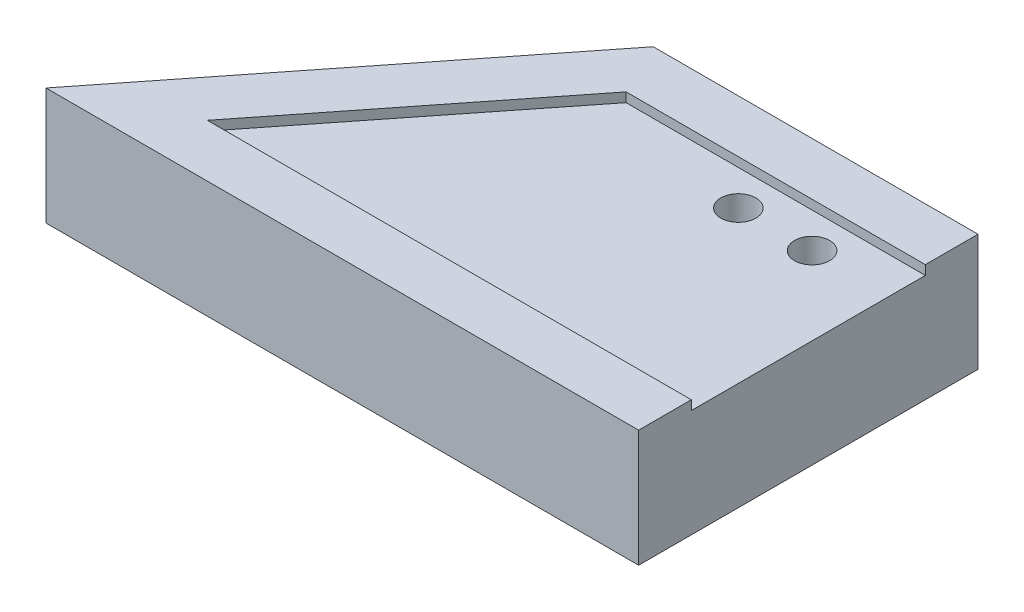
SolidWorks part; units mm, degrees
ref_plane "Front Plane" through (0, 0, 0) normal (0, 0, 1) x (1, 0, 0)
ref_plane "Top Plane" through (0, 0, 0) normal (0, 1, 0) x (1, 0, 0)
ref_plane "Right Plane" through (0, 0, 0) normal (1, 0, 0) x (0, 0, -1)
sketch "Sketch1" plane through (0, 0, 0) normal (0, 1, 0) x (1, 0, 0)
  line L0 (0, 0) -> (61, 0)
  line L1 (61, 0) -> (46, 19)
  line L2 (46, 19) -> (15, 19)
  line L3 (15, 19) -> (0, 0)
  line L4 (12.577, 24) -> (-10.3177, -5)
  line L5 (-10.3177, -5) -> (71.3177, -5)
  line L6 (71.3177, -5) -> (48.423, 24)
  line L7 (48.423, 24) -> (12.577, 24)
  point P3 (30.5, 19)
  point P7 (30.5, 0)
  dimension "D1" = 19
  dimension "D2" = 31
  dimension "D3" = 61
  dimension "D4" = 5
extrude "Boss-Extrude1" add sketch "Sketch1" along normal blind 10 contours L6 L7 L4 L5 L3 L2 L1 L0 | L2 L3 L0 L1 | L3 L0 L1 L2 | L4 L5 L6 L7 region at (30.5, 0, -8.4674) region at (30.5, 0, -23.1337)
sketch "Sketch2" plane through (0, 0, 0) normal (0, -1, 0) x (1, 0, 0)
  line L0 (46, -19) -> (15, -19) construction
  line L1 (46, -19) -> (15, -19)
  line L4 (0, 0) -> (61, 0) construction
  line L5 (0, 0) -> (61, 0)
  line L8 (14.7577, -19.5) -> (46.2423, -19.5)
  line L9 (46.2423, -19.5) -> (62.0318, 0.5)
  line L10 (62.0318, 0.5) -> (-1.0318, 0.5)
  line L11 (-1.0318, 0.5) -> (14.7577, -19.5)
  line L12 (14.7577, -19.5) -> (46.2423, -19.5)
  line L13 (46.2423, -19.5) -> (62.0318, 0.5)
  line L14 (62.0318, 0.5) -> (-1.0318, 0.5)
  line L15 (-1.0318, 0.5) -> (14.7577, -19.5)
  circle A0 centre (27.35, -16.5) radius 1.5
  circle A1 centre (33.65, -16.5) radius 1.5
  point P6 (30.5, 0)
  dimension "D2" = 3
  dimension "D3" = 3
  dimension "D4" = 3.15
  dimension "D5" = 3.15
  dimension "D6" = 2.5
  dimension "D1" = 0.5
extrude "Cut-Extrude1" cut sketch "Sketch2" along normal blind 0.8 from surface contours L14 L15 L12 L13 A1 A0 region at (30.5, 0, -8.2635) starting at face at (30.5, 10, -9.5)
extrude "Cut-Extrude2" cut sketch "Sketch2<3>" against normal blind 15 contours A0 | A1
sketch "Sketch2<3>" plane through (0, 0, 0) normal (0, -1, 0) x (1, 0, 0) same geometry as "Sketch2"
sketch "Sketch3" plane through (0, 0, 0) normal (0, -1, 0) x (1, 0, 0)
  line L0 (40.3302, 5) -> (40.3302, -24)
  line L1 (48.423, -24) -> (12.577, -24) construction
  line L2 (71.3177, 5) -> (48.423, -24) construction
  line L3 (-10.3177, 5) -> (71.3177, 5) construction
  line L4 (48.423, -24) -> (40.3302, -24)
  line L5 (71.3177, 5) -> (48.423, -24)
  line L6 (40.3302, 5) -> (71.3177, 5)
extrude "Cut-Extrude3" cut sketch "Sketch3" against normal through all
sketch "Sketch4" plane through (0, 0, 0) normal (0, -1, 0) x (1, 0, 0)
  line L1 (-0.6053, -17.802) -> (2.3257, -12.7255)
  line L2 (2.3257, -12.7255) -> (-0.6053, -7.649)
  line L3 (-0.6053, -7.649) -> (-6.4671, -7.649)
  line L4 (-6.4671, -7.649) -> (-9.3981, -12.7255)
  line L5 (-9.3981, -12.7255) -> (-6.4671, -17.802)
  line L6 (-6.4671, -17.802) -> (-0.6053, -17.802)
  circle A0 centre (-3.5362, -12.7255) radius 5.0765 construction
  point P1 (-1.1634, -11.8416)
  point P9 (-3.5362, -12.7255)
